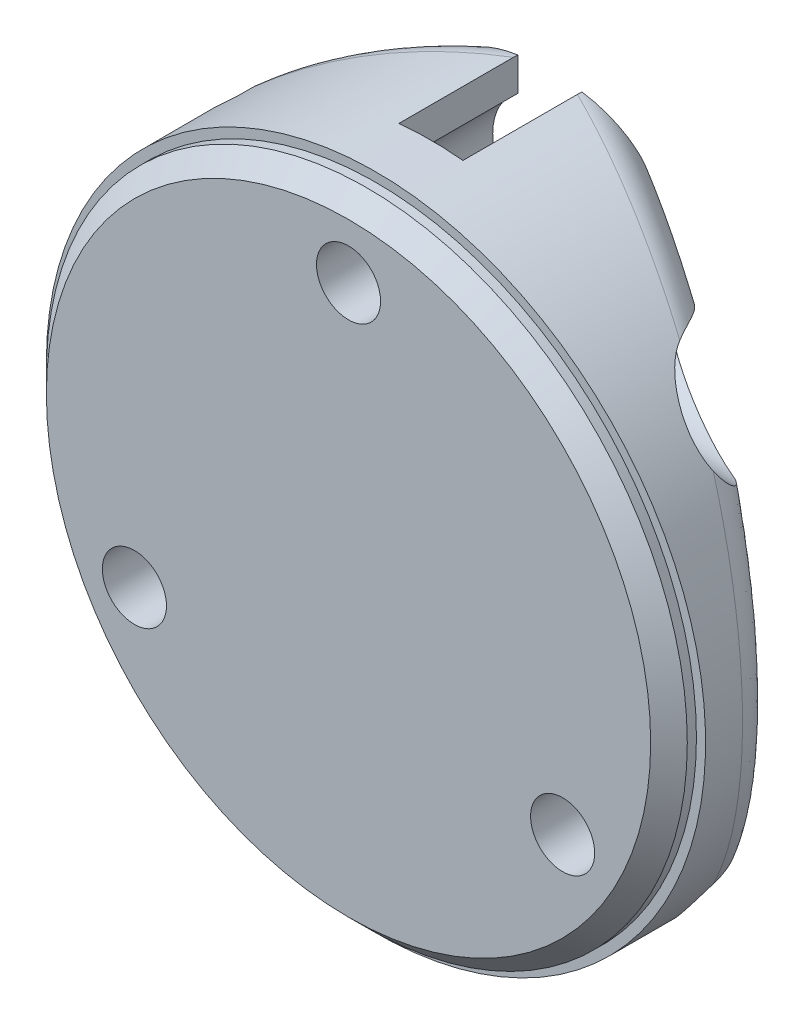
SolidWorks part; units mm, degrees
ref_plane "Front Plane" through (0, 0, 0) normal (0, 0, 1) x (1, 0, 0)
ref_plane "Top Plane" through (0, 0, 0) normal (0, 1, 0) x (1, 0, 0)
ref_plane "Right Plane" through (0, 0, 0) normal (1, 0, 0) x (0, 0, -1)
sketch "Sketch1" plane through (0, 0, 0) normal (0, 0, 1) x (1, 0, 0)
  circle A0 centre (0, 0) radius 17.5
  dimension "D1" = 35
extrude "Boss-Extrude1" add sketch "Sketch1" along normal blind 1.5
sketch "Sketch2" plane through (0, 0, 0) normal (0, 0, -1) x (-1, 0, 0)
  circle A0 centre (0, 0) radius 18
  dimension "D1" = 36
extrude "Boss-Extrude2" add sketch "Sketch2" along normal blind 3
chamfer "Chamfer1" distance 1 angle 45 1 edges at (17.5, 0, 1.5)
sketch "Sketch3" plane through (0, 0, 0) normal (0, 1, 0) x (1, 0, 0)
  line L0 (0, 0) -> (0, 9.5) construction
  line L1 (-18.5, 3) -> (-5.524, 9.5)
  line L2 (-5.524, 9.5) -> (-1.75, 9.5)
  line L3 (-1.75, 9.5) -> (-1.75, 3)
  line L4 (18, 3) -> (-18, 3) construction
  line L5 (-18.5, 3) -> (-1.75, 3)
  line L6 (18.5, 3) -> (1.75, 3)
  line L7 (1.75, 9.5) -> (1.75, 3)
  line L8 (5.524, 9.5) -> (1.75, 9.5)
  line L9 (18.5, 3) -> (5.524, 9.5)
  line L10 (18, 3) -> (-18, 3) construction
  dimension "D1" = 3.5
  dimension "D2" = 6.5
extrude "Boss-Extrude3" add sketch "Sketch3" along normal mid plane 40
sketch "Sketch4" plane through (0, 0, 0) normal (1, 0, 0) x (0, 0, -1)
  line L0 (5.75, 11) -> (5.75, -11) construction
  line L1 (9.5, 20) -> (9.5, -20) construction
  circle A0 centre (5.75, 11) radius 1.5
  circle A1 centre (5.75, -11) radius 1.5
  point P4 (5.75, 0)
  dimension "D1" = 3
  dimension "D2" = 22
  dimension "D3" = 3.75
extrude "Cut-Extrude1" cut sketch "Sketch4" against normal through all both and the other way through all
sketch "Sketch6" plane through (0, 0, 1.5) normal (0, 0, 1) x (1, 0, 0)
  line L1 (23.3622, -22.945) -> (-23.3622, -22.945)
  line L2 (23.3622, -22.945) -> (23.3622, 22.945)
  line L3 (23.3622, 22.945) -> (-23.3622, 22.945)
  line L4 (-23.3622, -22.945) -> (-23.3622, 22.945)
  line L5 (23.3622, -22.945) -> (-23.3622, 22.945) construction
  line L6 (23.3622, 22.945) -> (-23.3622, -22.945) construction
  circle A0 centre (0, 0) radius 18
  arc A1 (1.75, -17.9147) -> (1.75, 17.9147) centre (0, 0) ccw construction
extrude "Cut-Extrude2" cut sketch "Sketch6" against normal through all both and the other way through all
sketch "Sketch7" plane through (0, 0, -3) normal (0, 0, -1) x (-1, 0, 0)
  line L0 (1.75, 17.9147) -> (1.75, -17.9147) construction
  line L1 (-1.75, 7) -> (1.75, 7)
  line L2 (-1.75, 7) -> (-1.75, -7)
  line L3 (-1.75, -7) -> (1.75, -7)
  line L4 (1.75, 7) -> (1.75, -7)
  line L5 (-1.75, 7) -> (1.75, -7) construction
  line L6 (-1.75, -7) -> (1.75, 7) construction
  point P0 (0, 0)
  dimension "D1" = 14
extrude "Cut-Extrude3" cut sketch "Sketch7" against normal blind 3
sketch "Sketch8" plane through (0, 0, 0) normal (1, 0, 0) x (0, 0, -1)
  circle A0 centre (5.75, 11) radius 2.75
  circle A1 centre (5.75, -11) radius 2.75
  dimension "D1" = 5.5
extrude "Cut-Extrude4" cut sketch "Sketch8" along normal blind 33 from offset 6
sketch "Sketch9" plane through (0, 0, 0) normal (1, 0, 0) x (0, 0, -1)
  line L1 (7.3377, 8.25) -> (8.9254, 11)
  line L2 (8.9254, 11) -> (7.3377, 13.75)
  line L3 (7.3377, 13.75) -> (4.1623, 13.75)
  line L4 (4.1623, 13.75) -> (2.5746, 11)
  line L5 (2.5746, 11) -> (4.1623, 8.25)
  line L6 (4.1623, 8.25) -> (7.3377, 8.25)
  line L7 (4.1623, -13.75) -> (7.3377, -13.75)
  line L8 (7.3377, -13.75) -> (8.9254, -11)
  line L9 (8.9254, -11) -> (7.3377, -8.25)
  line L10 (7.3377, -8.25) -> (4.1623, -8.25)
  line L11 (4.1623, -8.25) -> (2.5746, -11)
  line L12 (2.5746, -11) -> (4.1623, -13.75)
  circle A0 centre (5.75, 11) radius 2.75 construction
  circle A1 centre (5.75, -11) radius 2.75 construction
  dimension "D1" = 5.5
extrude "Cut-Extrude5" cut sketch "Sketch9" against normal blind 33 from offset 5 offset against normal yes
fillet "Fillet1" radius 2 6 edges at (8.7882, 15.7089, -7.8649) (18, 0, -3.2505) (8.7882, -15.7089, -7.8649) (-8.7353, -15.7383, -7.8914) (-8.7353, 15.7383, -7.8914) (-18, 0, -3.2505)
sketch "Sketch10" plane through (0, 0, 1.5) normal (0, 0, 1) x (1, 0, 0)
  line L0 (0, 13.5) -> (11.6913, -6.75) construction
  line L1 (11.6913, -6.75) -> (-11.6913, -6.75) construction
  line L2 (-11.6913, -6.75) -> (0, 13.5) construction
  circle A0 centre (0, 0) radius 13.5 construction
  circle A1 centre (0, 13.5) radius 1.75
  circle A2 centre (11.6913, -6.75) radius 1.75
  circle A3 centre (-11.6913, -6.75) radius 1.75
  dimension "D1" = 27
  dimension "D2" = 3.5
extrude "Cut-Extrude6" cut sketch "Sketch10" against normal through all
sketch "Sketch12" plane through (0, 0, -9.5) normal (0, 0, -1) x (-1, 0, 0)
  circle A0 centre (-11.6913, -6.75) radius 3.125
  circle A1 centre (0, 13.5) radius 3.125
  circle A2 centre (11.6913, -6.75) radius 3.125
  dimension "D1" = 6.25
extrude "Cut-Extrude7" cut sketch "Sketch12" against normal blind 6
sketch "Sketch13" plane through (0, 0, 0) normal (1, 0, 0) x (0, 0, -1)
  circle A0 centre (38, 0) radius 31.5
  dimension "D1" = 63
  dimension "D2" = 38
extrude "Cut-Extrude8" cut sketch "Sketch13" against normal blind 22 from offset 6 offset against normal yes
